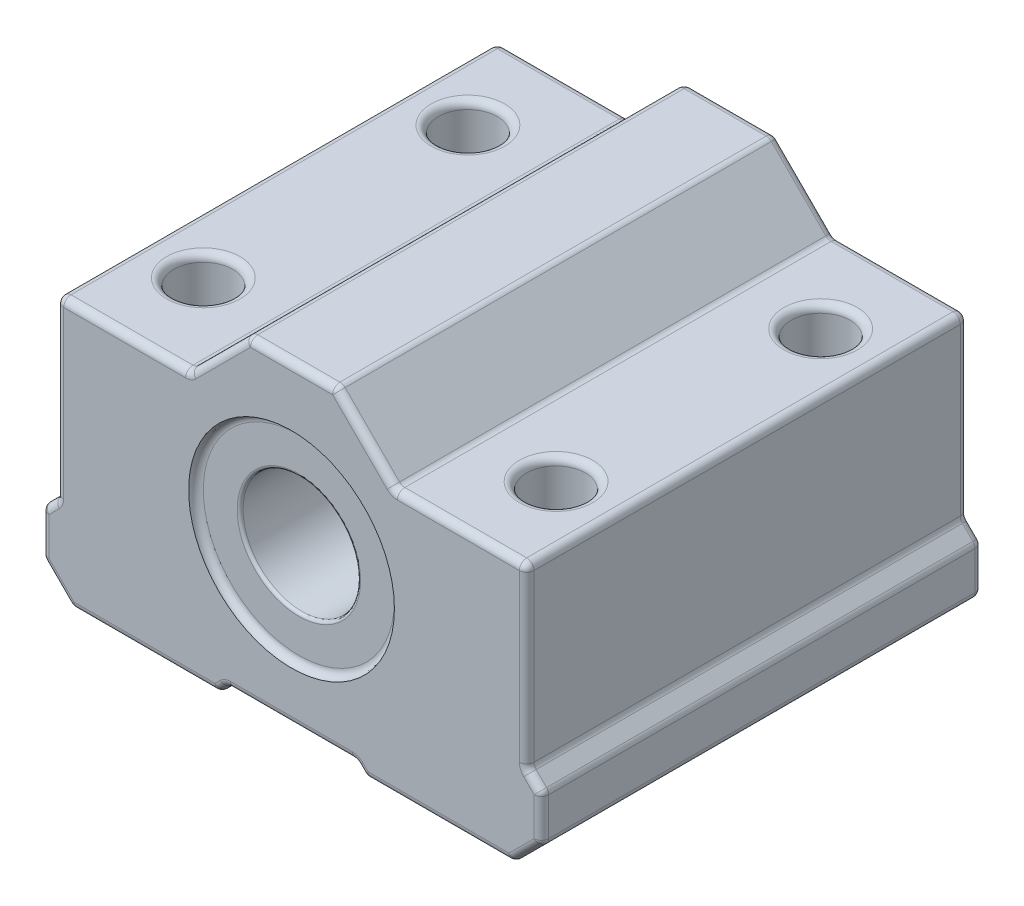
SolidWorks part; units mm, degrees
other "Camera1"
material "1060 Alloy"
ref_plane "Front Plane" through (0, 0, 0) normal (0, 0, 1) x (1, 0, 0)
ref_plane "Top Plane" through (0, 0, 0) normal (0, 1, 0) x (1, 0, 0)
ref_plane "Right Plane" through (0, 0, 0) normal (1, 0, 0) x (0, 0, -1)
sketch "Sketch1" plane through (0, 0, 0) normal (0, 0, 1) x (1, 0, 0)
  line L0 (-7, 0) -> (-7, 7) construction
  line L1 (-17, -11) -> (-4, -11)
  line L2 (-17, -11) -> (-17, -5)
  line L3 (-3, 11) -> (3, 11)
  line L4 (17, -11) -> (17, -5)
  line L5 (-17, -11) -> (10.8182, 7) construction
  line L6 (-10.8182, 7) -> (17, -11) construction
  line L7 (-7, 7) -> (7, 7) construction
  line L8 (7, 7) -> (7, 0) construction
  line L9 (-7, 7) -> (-16.0014, 7)
  line L10 (-16.0014, 7) -> (-7, 7)
  line L11 (7, 7) -> (16, 7)
  line L12 (-7, 7) -> (-3, 11)
  line L13 (7, 7) -> (3, 11)
  line L14 (0, 0) -> (0, -11) construction
  line L15 (17, 7) -> (16, 7) construction
  line L16 (-16.0014, -11) -> (-16.0014, -5) construction
  line L17 (-16.0014, -5) -> (-17, -5)
  line L18 (-17, -5) -> (-17, -11)
  line L19 (-16.0014, 7) -> (-16.0014, -5)
  line L20 (16, 7) -> (16, -5) construction
  line L21 (16, -10.3529) -> (16, -11)
  line L22 (16, -11) -> (16, -10.3529)
  line L23 (17, -5) -> (16, -5)
  line L24 (16, 7) -> (16, -5)
  line L25 (0, -11) -> (0, -10.3529) construction
  line L26 (-4, -10.3529) -> (4, -10.3529)
  line L27 (4, -10.3529) -> (4, -11)
  line L29 (-4, -11) -> (-4, -10.3529)
  line L30 (4, -11) -> (17, -11)
  circle A0 centre (0, 0) radius 4
  circle A1 centre (0, 0) radius 7 construction
  point P6 (0, 0)
  point P30 (0, -10.3529)
  dimension "D1" = 18
  dimension "D2" = 10
  dimension "D3" = 34
  dimension "D4" = 11
extrude "Boss-Extrude1" add sketch "Sketch1" along normal blind 30 contours L24 L11 L13 L3 L12 L9 L19 L17 L2 L1 L4 L23 A0 region at (-16.595, -8, 0)
chamfer "Chamfer1" distance 2 angle 45 2 edges at (-17, -11, 15) (17, -11, 15)
chamfer "Chamfer2" distance 1 angle 45 4 edges at (17, -5, 15) (-17, -5, 15) (-4, -11, 15) (4, -11, 15)
fillet "Fillet1" radius 0.5 56 edges at (15, -11, 15) (5, -11, 15) (-4.3529, -10.3529, 15) (4.3529, -10.3529, 15) (-17, -9, 15) (-17, -6, 15) (-15, -11, 15) (-5, -11, 15) (4, 0, 0) (5, 9, 0) (-5, 9, 0) (-16.5007, -5.5007, 0) (-17, -7.5, 0) (-16, -10, 0) (-10, -11, 0) (-4.6765, -10.6765, 0) (0, -10.3529, 0) (4.6765, -10.6765, 0) (10, -11, 0) (16, -10, 0) (16.5, -5.5, 0) (17, -9, 15) (17, -6, 15) (17, -7.5, 0) (16, -5, 15) (16, 1, 0) (16, 7, 15) (7, 7, 15) (11.5, 7, 0) (4, 0, 30) (16, -10, 30) (10, -11, 30) (4.6765, -10.6765, 30) (0, -10.3529, 30) (-4.6765, -10.6765, 30) (-10, -11, 30) (-16, -10, 30) (-17, -7.5, 30) (-16.5007, -5.5007, 30) (-5, 9, 30) (5, 9, 30) (11.5, 7, 30) (16, 1, 30) (16.5, -5.5, 30) (17, -7.5, 30) (3, 11, 15) (0, 11, 30) (-3, 11, 15) (0, 11, 0) (-7, 7, 15) (-11.5007, 7, 30) (-11.5007, 7, 0) (-16.0014, 7, 15) (-16.0014, 0.9993, 30) (-16.0014, -5.0014, 15) (-16.0014, 0.9993, 0)
sketch "Sketch2" plane through (0, 0, 0) normal (0, 0, -1) x (-1, 0, 0)
  circle A0 centre (0, 0) radius 7
  circle A1 centre (0, 0) radius 3
extrude "Cut-Extrude1" cut sketch "Sketch2" against normal blind 0.5
sketch "Sketch3" plane through (0, 0, 30) normal (0, 0, 1) x (1, 0, 0)
  circle A0 centre (0, 0) radius 7
extrude "Cut-Extrude2" cut sketch "Sketch3" against normal blind 0.5
fillet "Fillet2" radius 0.5 2 edges at (7, 0, 29.5) (-7, 0, 0)
sketch "Sketch4" plane through (0, -11, 0) normal (0, -1, 0) x (1, 0, 0)
  line L0 (14.7929, 0.5) -> (-14.7929, 29.5) construction
  line L2 (12, 24) -> (-12, 24) construction
  line L3 (12, 24) -> (12, 6) construction
  line L4 (12, 6) -> (-12, 6) construction
  line L5 (-12, 24) -> (-12, 6) construction
  line L6 (12, 24) -> (-12, 6) construction
  line L7 (12, 6) -> (-12, 24) construction
  circle A0 centre (-12, 6) radius 2
  circle A1 centre (12, 6) radius 2
  circle A2 centre (12, 24) radius 2
  circle A3 centre (-12, 24) radius 2
  point P4 (0, 15)
  point P15 (-12.3784, 23.9243)
  dimension "D1" = 24
  dimension "D2" = 18
extrude "Cut-Extrude3" cut sketch "Sketch4" against normal blind 30
fillet "Fillet4" radius 0.2 2 edges at (-4, 0, 29.5) (4, 0, 0.5)
fillet "Fillet5" radius 0.5 8 edges at (12, -11, 4) (12, -11, 22) (-12, -11, 4) (-12, -11, 22) (12, 7, 26) (12, 7, 8) (-12, 7, 4) (-12, 7, 22)
